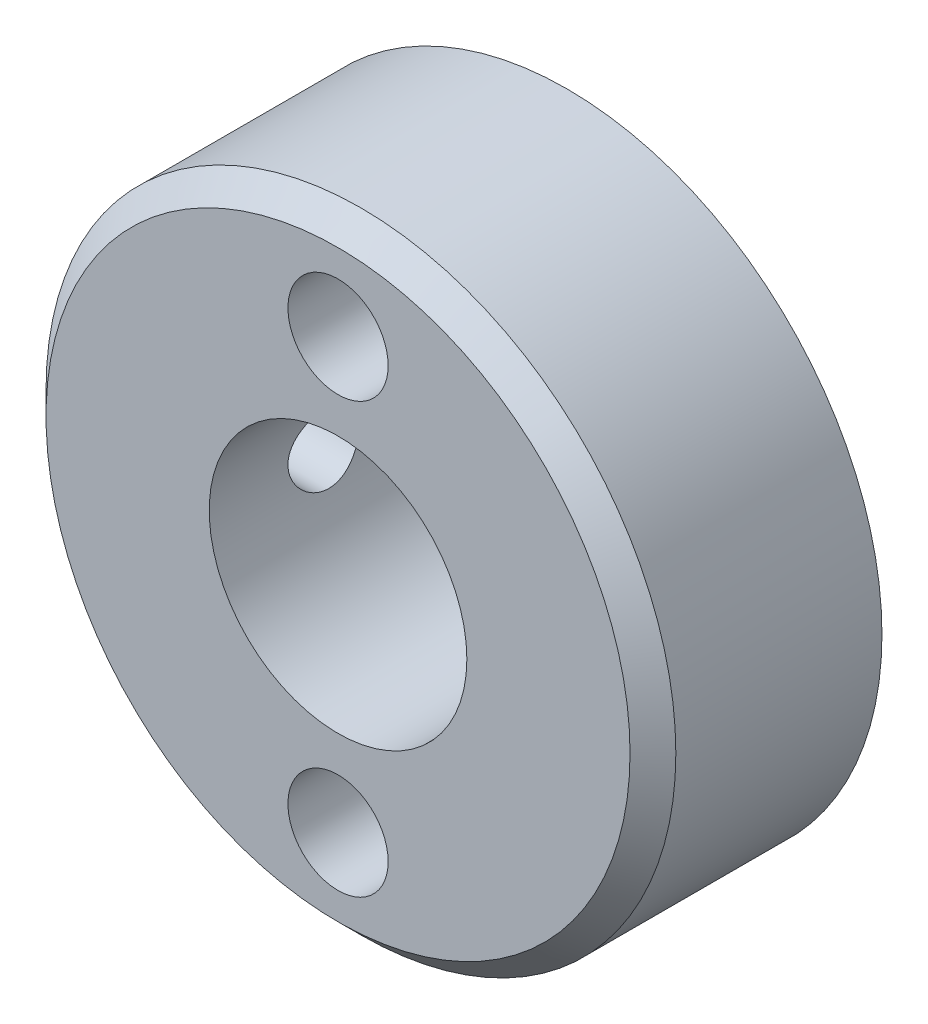
SolidWorks part; units mm, degrees
ref_plane "Front" through (0, 0, 0) normal (0, 0, 1) x (1, 0, 0)
ref_plane "Top" through (0, 0, 0) normal (0, 1, 0) x (1, 0, 0)
ref_plane "Right" through (0, 0, 0) normal (1, 0, 0) x (0, 0, -1)
sketch "Sketch1" plane through (0, 0, 0) normal (0, 0, 1) x (1, 0, 0)
  circle A0 centre (0, 0) radius 11
  circle A1 centre (0, 0) radius 4.5
  dimension "D2" = 9
extrude "BaseNut" add sketch "Sketch1" against normal blind 8
cosmetic thread "ThreadCosmetic1" [suppressed] parameters "D2"=10
sketch "Sketch5" plane through (0, 0, 0) normal (1, 0, 0) x (0, 0, -1)
  line L0 (-26.3849, 0) -> (32.989, 0) construction
  line L1 (-6.0703, 7.5) -> (6.0703, 7.5) construction
  line L2 (0, 7.5) -> (0, 9.25)
  line L3 (0, 11) -> (0, -11) construction
  line L4 (0, 9.25) -> (4, 9.25)
  line L5 (4, 9.25) -> (5.0104, 7.5)
  line L6 (5.0104, 7.5) -> (0, 7.5)
  dimension "d1" = 3.5
  dimension "D2" = 60
  dimension "t" = 4
  dimension "B" = 15
revolve "Cut-Revolve1" cut sketch "Sketch5" angle 360 about L1
chamfer "Chamfer1" distance 0.8 angle 45 2 edges at (11, 0, 0) (4.5, 0, -8)
sketch "Sketch3" plane through (0, 0, 0) normal (1, 0, 0) x (0, -1, 0)
  circle A0 centre (0, 4) radius 1.25
  dimension "d2" = 2.5
  dimension "K" = 4
extrude "Cut-Extrude1" cut sketch "Sketch3" against normal through all
cosmetic thread "ThreadCosmetic2" [suppressed] parameters "D3"=3
mirror "Mirror1" about plane through (0, 0, 0) normal (0, 1, 0) of "Cut-Revolve1"
sketch "Sketch6" plane through (0, 0, 0) normal (0, 1, 0) x (1, 0, 0)
  line L0 (0, 11.6242) -> (0, -3.0108) construction
  line L1 (4, 7.45) -> (4, 6.95)
  line L2 (4, 6.95) -> (4.5, 6.95)
  line L3 (4.5, 6.95) -> (4.933, 7.2)
  line L4 (4.933, 7.2) -> (4.5, 7.45)
  line L5 (4.5, 7.45) -> (4, 7.45)
  line L6 (4.5, 7.2) -> (-4.5, 7.2) construction
  dimension "D1" = 0.5
  dimension "D2" = 9
revolve "Cut-Revolve10" [suppressed] cut sketch "Sketch6" angle 360 about L0
pattern_linear "LPattern10" [suppressed] count 13 spacing 0.6 along (0, 0, 1) of bodies 107
equation "\"D2@Sketch6\" = \"D2@Sketch1\""
equation "\"D1@Sketch6\" = (  \"D2@ThreadCosmetic1\" - \"D2@Sketch1\" )  / 2"
equation "\"D3@LPattern10\" = \"D1@Sketch6\" * 1.2"
equation "\"D1@LPattern10\" = \"m@BaseNut\" / \"D3@LPattern10\""
